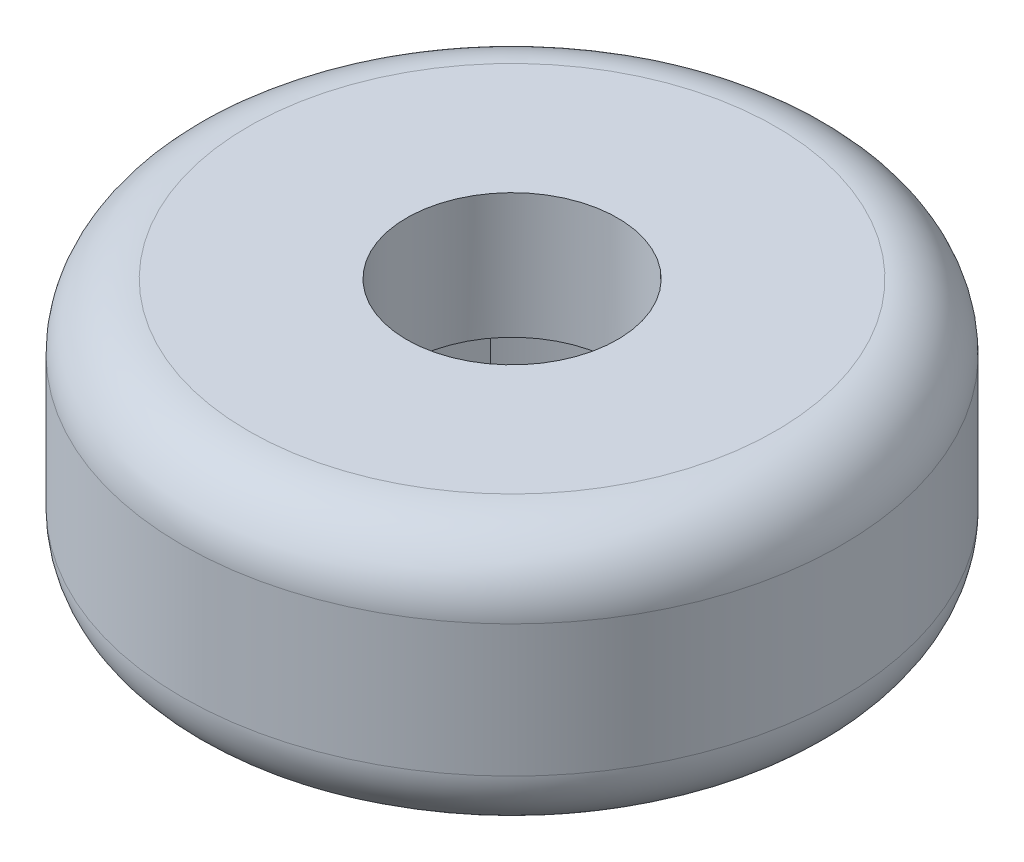
SolidWorks part; units mm, degrees
ref_plane "正面" through (0, 0, 0) normal (0, 0, 1) x (1, 0, 0)
ref_plane "平面" through (0, 0, 0) normal (0, 1, 0) x (1, 0, 0)
ref_plane "右側面" through (0, 0, 0) normal (1, 0, 0) x (0, 0, -1)
sketch "ｽｹｯﾁ1" plane through (0, 0, 0) normal (0, 1, 0) x (1, 0, 0)
  line L1 (-77.1853, 15.9281) -> (-72.9853, 15.9281)
  line L2 (-77.1853, 15.9281) -> (-77.1853, 11.3674)
  line L3 (-77.1853, 11.3674) -> (-72.9853, 11.3674)
  line L4 (-72.9853, 15.9281) -> (-72.9853, 11.3674)
  line L5 (-77.1853, 15.9281) -> (-72.9853, 11.3674) construction
  line L6 (-77.1853, 11.3674) -> (-72.9853, 15.9281) construction
  circle A0 centre (-75.0853, 13.6477) radius 3.1
  circle A1 centre (-75.0853, 13.6477) radius 5
  dimension "D1" = 6.2
  dimension "D3" = 10
  dimension "D2" = 4.2
extrude "ﾎﾞｽ - 押し出し1" add sketch "ｽｹｯﾁ1" along normal blind 4 contours A1 A0 | L4 A0 | L2 A0 | L1 A0 | L4 L1 L2 L3 | L3 A0 region at (-75.0853, 0, -16.26) region at (-75.0853, 0, -13.6477) region at (-77.5914, 0, -13.6477) region at (-72.5792, 0, -13.6477) region at (-75.0853, 0, -11.0355) region at (-79.9439, 0, -13.6477)
sketch "ｽｹｯﾁ2" plane through (0, 0, 0) normal (0, -1, 0) x (1, 0, 0)
  line L3 (-77.4353, -11.626) -> (-72.7353, -11.626)
  line L4 (-77.4353, -11.626) -> (-77.4353, -15.6695)
  line L5 (-77.4353, -15.6695) -> (-72.7353, -15.6695)
  line L6 (-72.7353, -11.626) -> (-72.7353, -15.6695)
  line L7 (-77.4353, -11.626) -> (-72.7353, -15.6695) construction
  line L8 (-77.4353, -15.6695) -> (-72.7353, -11.626) construction
  circle A0 centre (-75.0853, -13.6477) radius 3.1 construction
  circle A1 centre (-75.0853, -13.6477) radius 3.1
  dimension "D1" = 4.7
extrude "ｶｯﾄ - 押し出し1" cut sketch "ｽｹｯﾁ2" against normal blind 2.1 contours L6 L3 L4 L5 | L3 A1 | L5 A1 region at (-75.0853, 0, -11.1875) region at (-75.0853, 0, -13.6477) region at (-75.0853, 0, -16.1079)
sketch "ｽｹｯﾁ3" plane through (0, 4, 0) normal (0, 1, 0) x (1, 0, 0)
  circle A0 centre (0, 0) radius 1.6
  circle A1 centre (-75.0853, 13.6477) radius 1.6
  circle A2 centre (-75.0853, 13.6477) radius 5
  circle A3 centre (-75.0853, 13.6477) radius 5
  dimension "D1" = 3.2
  dimension "D3" = 3.2
  dimension "D2" = 0
extrude "ｶｯﾄ - 押し出し2" cut sketch "ｽｹｯﾁ3" against normal blind 3 contours A1 region at (-75.0853, 4, -13.6477)
fillet "ﾌｨﾚｯﾄ1" radius 1 2 edges at (-75.0853, 0, -8.6477) (-75.0853, 4, -8.6477)
